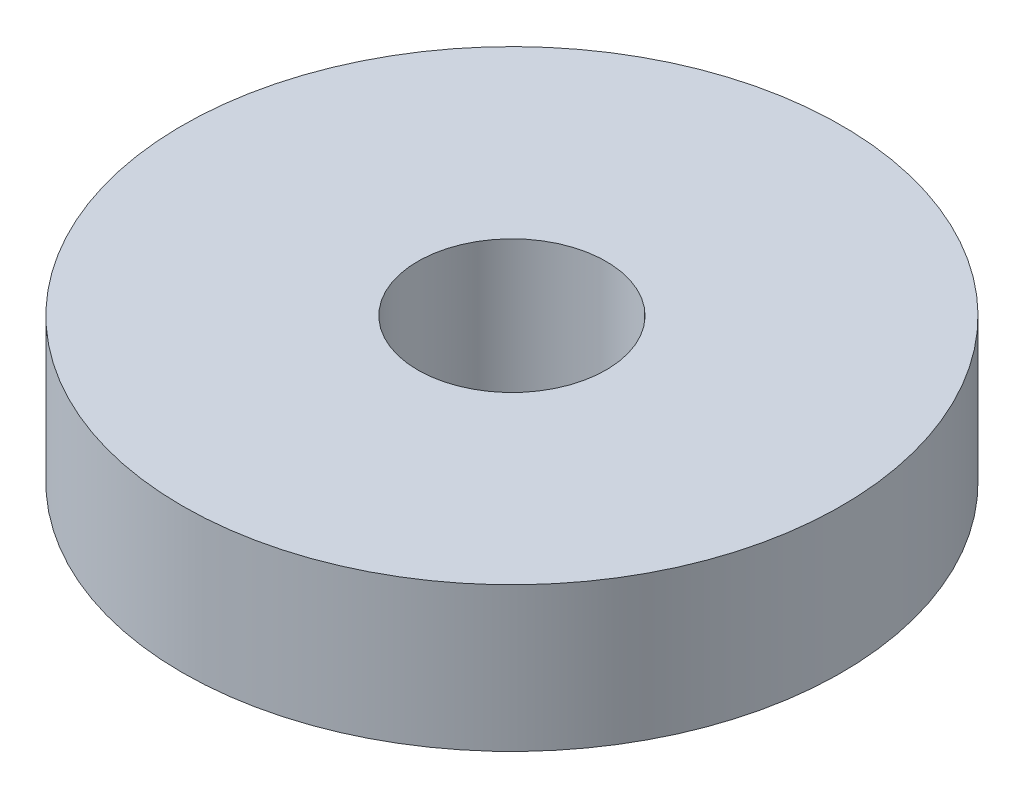
SolidWorks part; units mm, degrees
ref_plane "Front Plane" through (0, 0, 0) normal (0, 0, 1) x (1, 0, 0)
ref_plane "Top Plane" through (0, 0, 0) normal (0, 1, 0) x (1, 0, 0)
ref_plane "Right Plane" through (0, 0, 0) normal (1, 0, 0) x (0, 0, -1)
sketch "Sketch1" plane through (0, 0, 0) normal (0, 1, 0) x (1, 0, 0)
  circle A0 centre (0, 0) radius 52.5
  dimension "FLANGE_OD" = 105
extrude "Boss-Extrude1" add sketch "Sketch1" along normal blind 23
sketch "Sketch2" plane through (0, 0, 0) normal (0, 1, 0) x (1, 0, 0)
  circle A0 centre (0, 0) radius 15
  dimension "BORE_D" = 30
extrude "Cut-Extrude1" cut sketch "Sketch2" along normal through all
sketch "Sketch3" plane through (0, 23, 0) normal (0, 1, 0) x (1, 0, 0)
  circle A0 centre (0, 0) radius 11.2102 construction
  circle A1 centre (-11.2102, 0) radius 1.5537
  dimension "BOLT_D" = 3.1075
  dimension "BOLT_PCD" = 22.4204
extrude "Cut-Extrude2" cut sketch "Sketch3" against normal blind 17.2855 rebuild error yes
pattern_circular "CirPattern1" count 5 over 360 rebuild error yes
